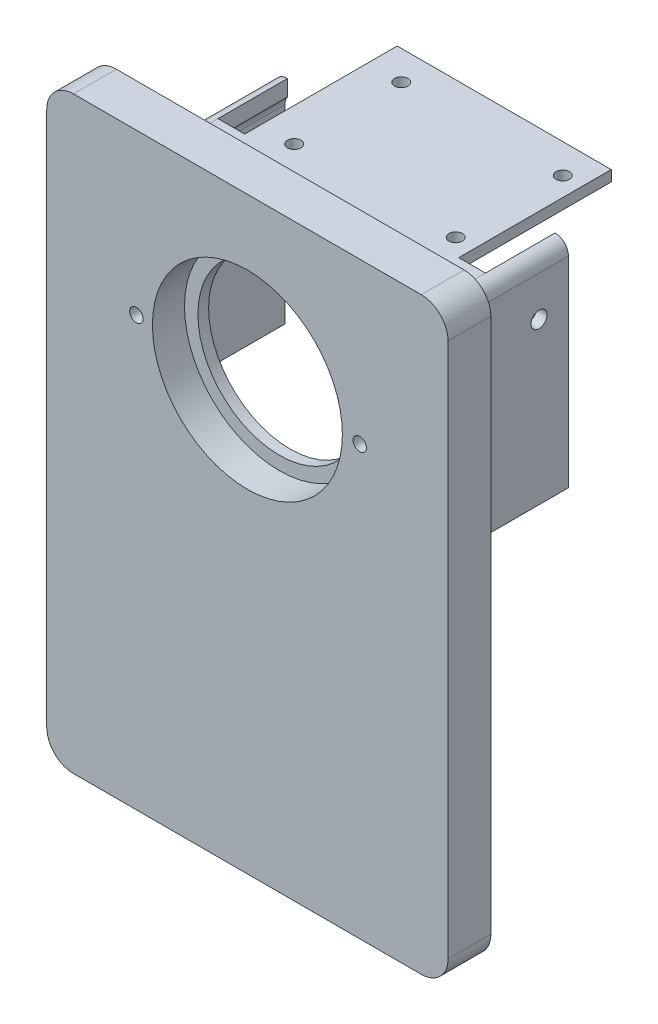
SolidWorks part; units mm, degrees
ref_plane "Alzado" through (0, 0, 0) normal (0, 0, 1) x (1, 0, 0)
ref_plane "Planta" through (0, 0, 0) normal (0, 1, 0) x (1, 0, 0)
ref_plane "Vista lateral" through (0, 0, 0) normal (1, 0, 0) x (0, 0, -1)
sketch "Croquis2" plane through (0, 0, 0) normal (0, 0, 1) x (1, 0, 0)
  line L1 (-65, 110) -> (65, 110)
  line L2 (-75, 100) -> (-75, -100)
  line L3 (-65, -110) -> (65, -110)
  line L4 (75, 100) -> (75, -100)
  line L5 (-75, 110) -> (75, -110) construction
  line L6 (-75, -110) -> (75, 110) construction
  arc A0 (-75, -100) -> (-65, -110) centre (-65, -100) ccw
  arc A1 (65, -110) -> (75, -100) centre (65, -100) ccw
  arc A2 (65, 110) -> (75, 100) centre (65, 100) cw
  arc A3 (-65, 110) -> (-75, 100) centre (-65, 100) ccw
  point P0 (0, 0)
  dimension "D3" = 10
  dimension "D1" = 220
  dimension "D2" = 150
extrude "Saliente-Extruir1" add sketch "Croquis2" along normal blind 16
sketch "Croquis3" plane through (0, 0, 16) normal (0, 0, 1) x (1, 0, 0)
  line L0 (65, 110) -> (-65, 110) construction
  circle A0 centre (0, 50) radius 30.5
  dimension "D1" = 60
  dimension "D2" = 61
sketch "Croquis4" plane through (0, 0, 16) normal (0, 0, 1) x (1, 0, 0)
  line L0 (65, 110) -> (-65, 110) construction
  circle A0 centre (0, 50) radius 35.5
  dimension "D1" = 60
extrude "Cortar-Extruir3" cut sketch "Croquis3" against normal through all
extrude "Cortar-Extruir4" cut sketch "Croquis4" against normal blind 12
sketch "Croquis5" plane through (0, 0, 0) normal (0, 0, -1) x (-1, 0, 0)
  line L0 (-55, 10) -> (-51, 10)
  line L1 (55, 10) -> (51, 10)
  line L2 (55, 10) -> (55, 83)
  line L3 (-55, 10) -> (-55, 83)
  line L4 (-48, 90) -> (48, 90)
  line L5 (51, 10) -> (51, 79)
  line L6 (-51, 10) -> (-51, 79)
  line L7 (-44, 86) -> (44, 86)
  line L8 (55, 83) -> (55, 10)
  line L9 (-55, 10) -> (-55, 83)
  line L10 (-51, 86) -> (-51, 79)
  line L11 (-51, 86) -> (-44, 86)
  line L12 (-55, 83) -> (-55, 90)
  line L13 (-55, 90) -> (-48, 90)
  line L14 (44, 86) -> (51, 86)
  line L15 (51, 86) -> (51, 79)
  line L16 (55, 83) -> (55, 90)
  line L17 (55, 90) -> (48, 90)
  point P11 (55, 90)
  point P14 (-55, 90)
  dimension "D1" = 4
  dimension "D2" = 55
  dimension "D3" = 55
  dimension "D4" = 80
  dimension "D5" = 80
extrude "Saliente-Extruir2" add sketch "Croquis5" along normal blind 49 contours L7 L5 L1 L2 L4 L3 L0 L6 region at (53.6399, 46.5, 0)
sketch "Croquis6" plane through (0, 90, 0) normal (0, 1, 0) x (1, 0, 0)
  line L0 (55, 49) -> (-55, 49) construction
  line L1 (-40, 80) -> (40, 80)
  line L2 (-40, 80) -> (-40, 18)
  line L3 (-40, 18) -> (40, 18)
  line L4 (40, 80) -> (40, 18)
  line L5 (-40, 80) -> (40, 18) construction
  line L6 (-40, 18) -> (40, 80) construction
  point P0 (0, 49)
  dimension "D1" = 80
  dimension "D2" = 31
extrude "Saliente-Extruir4" add sketch "Croquis6" against normal blind 4
sketch "Croquis8" plane through (0, 90, 0) normal (0, 1, 0) x (1, 0, 0)
  line L0 (-55, 49) -> (-40, 49) construction
  line L1 (-50, 57.6667) -> (-40, 57.6667)
  line L2 (-50, 57.6667) -> (-50, 23)
  line L3 (-50, 23) -> (-40, 23)
  line L4 (-40, 57.6667) -> (-40, 23)
  line L5 (-50, 57.6667) -> (-40, 23) construction
  line L6 (-50, 23) -> (-40, 57.6667) construction
  line L7 (0, 0) -> (0, 85.571) construction
  line L8 (65, 0) -> (-65, 0) construction
  line L9 (50, 57.6667) -> (40, 57.6667)
  line L10 (50, 23) -> (40, 23)
  line L11 (50, 57.6667) -> (50, 23)
  line L12 (40, 57.6667) -> (40, 23)
  point P0 (-47.5, 49)
  dimension "D1" = 10
  dimension "D2" = 26
extrude "Cortar-Extruir6" cut sketch "Croquis8" against normal through all
sketch "Croquis9" plane through (55, 0, 0) normal (1, 0, 0) x (0, 0, -1)
  line L0 (49, 90) -> (0, 90) construction
  line L1 (0, 10) -> (0, 90) construction
  circle A0 centre (38, 70) radius 3
  dimension "D1" = 20
  dimension "D2" = 38
extrude "Cortar-Extruir7" cut sketch "Croquis9" against normal through all
fillet "Redondeo1" radius 5 4 edges at (-51, 86, -24.5) (51, 86, -24.5) (55, 90, -24.5) (-55, 90, -24.5)
sketch "Croquis10" plane through (0, 0, 0) normal (0, 0, -1) x (-1, 0, 0)
  line L0 (0, 50) -> (108.5792, 50) construction
  circle A0 centre (-42, 50.158) radius 2.5
  circle A1 centre (41.5, 50.158) radius 2.5
  dimension "D3" = 5
  dimension "D4" = 5
  dimension "D1" = 83.5
  dimension "D2" = 42
extrude "Cortar-Extruir8" cut sketch "Croquis10" against normal through all
sketch "Croquis11" plane through (0, 86, 0) normal (0, -1, 0) x (1, 0, 0)
  circle A0 centre (32.8517, -29) radius 2.5
  circle A1 centre (32.8517, -69) radius 2.5
  circle A2 centre (-27.5163, -69) radius 2.5
  circle A3 centre (-27.5163, -29) radius 2.5
  dimension "D4" = 5
  dimension "D5" = 5
  dimension "D6" = 5
  dimension "D7" = 5
  dimension "D1" = 40
  dimension "D2" = 40
  dimension "D3" = 20
extrude "Cortar-Extruir9" cut sketch "Croquis11" against normal blind 10
